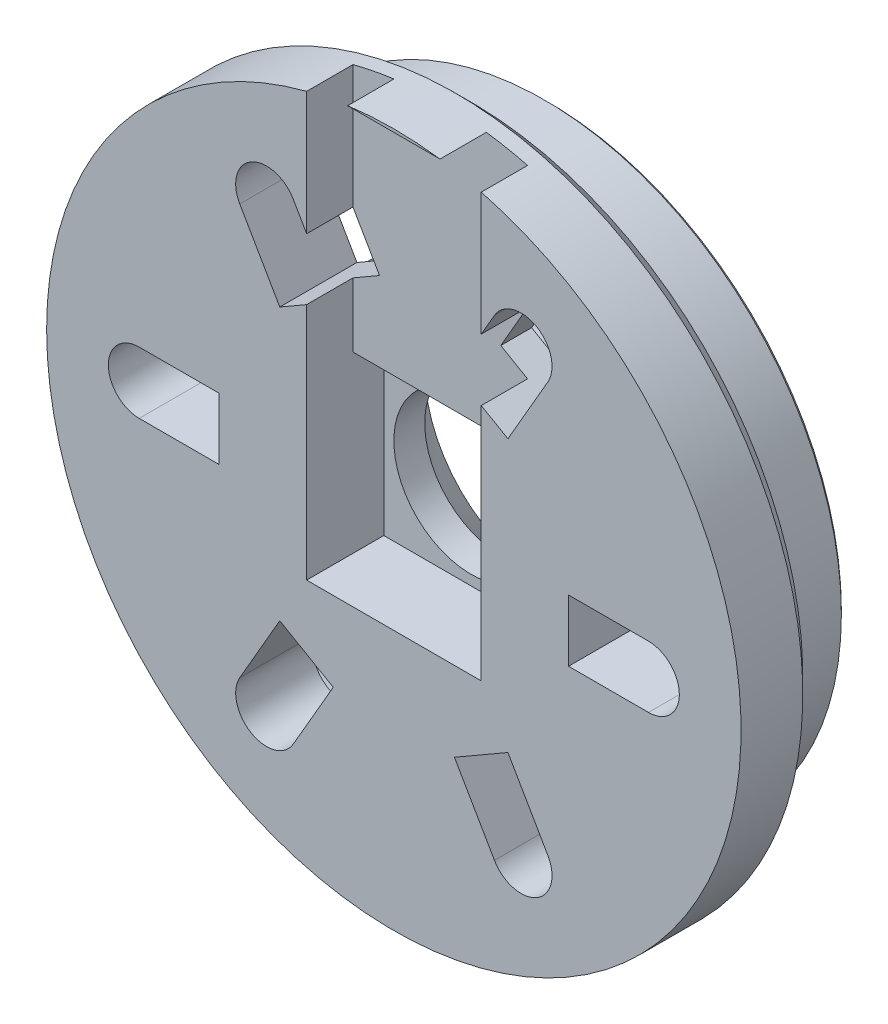
SolidWorks part; units mm, degrees
ref_plane "Front Plane" through (0, 0, 0) normal (0, 0, 1) x (1, 0, 0)
ref_plane "Top Plane" through (0, 0, 0) normal (0, 1, 0) x (1, 0, 0)
ref_plane "Right Plane" through (0, 0, 0) normal (1, 0, 0) x (0, 0, -1)
sketch "Sketch1" plane through (0, 0, 0) normal (0, 0, 1) x (1, 0, 0)
  circle A0 centre (0, 0) radius 9.8
  circle A1 centre (0, 0) radius 5
  dimension "D1" = 19.6
  dimension "D2" = 10
extrude "Boss-Extrude1" add sketch "Sketch1" along normal blind 10
sketch "Sketch2" plane through (0, 0, 10) normal (0, 0, 1) x (1, 0, 0)
  line L1 (-5.65, 5.65) -> (5.65, 5.65)
  line L2 (-5.65, 5.65) -> (-5.65, -5.65)
  line L3 (-5.65, -5.65) -> (5.65, -5.65)
  line L4 (5.65, 5.65) -> (5.65, -5.65)
  point P4 (5.65, 0)
  point P5 (0, 5.65)
  dimension "D1" = 11.3
  dimension "D2" = 11.3
extrude "Cut-Extrude1" cut sketch "Sketch2" against normal blind 5
sketch "Sketch3" plane through (0, 0, 10) normal (0, 0, 1) x (1, 0, 0)
  line L1 (-5.65, 5.65) -> (5.6634, 5.65)
  line L2 (-5.65, 5.65) -> (-5.65, 10.3571)
  line L3 (-5.65, 10.3571) -> (5.6634, 10.3571)
  line L4 (5.6634, 5.65) -> (5.6634, 10.3571)
extrude "Cut-Extrude2" cut sketch "Sketch3" against normal blind 3
sketch "Sketch4" plane through (0, 0, 10) normal (0, 0, 1) x (1, 0, 0)
  line L1 (-13.2922, 9.0382) -> (-7.8874, 9.0382)
  line L2 (-13.2922, 9.0382) -> (-13.2922, -9.0382)
  line L3 (-13.2922, -9.0382) -> (-7.8874, -9.0382)
  line L4 (-7.8874, 9.0382) -> (-7.8874, -9.0382)
  line L5 (13.4474, 9.0382) -> (7.784, 9.0382)
  line L6 (13.4474, 9.0382) -> (13.4474, -8.9089)
  line L7 (13.4474, -8.9089) -> (7.784, -8.9089)
  line L8 (7.784, 9.0382) -> (7.784, -8.9089)
extrude "Cut-Extrude3" cut sketch "Sketch4" against normal blind 3
chamfer "Chamfer1" distance 3 angle 45 1 edges at (5, 0, 0)
ref_plane "Plane1" through (0, 0, 5) normal (0, 0, -1) x (-1, 0, 0)
sketch "Sketch5" plane through (0, 0, 5) normal (0, 0, -1) x (-1, 0, 0)
  circle A0 centre (0, 0) radius 9.8
  circle A1 centre (0, 0) radius 22.5
  dimension "D1" = 12.7
extrude "Boss-Extrude2" add sketch "Sketch5" against normal blind 1
sketch "Sketch6" plane through (0, 0, 5) normal (0, 0, -1) x (-1, 0, 0)
  circle A0 centre (0, 0) radius 9.8
  circle A1 centre (0, 0) radius 11.25
  dimension "D1" = 22.5
extrude "Boss-Extrude3" add sketch "Sketch6" along normal up to surface (5 mm away) up to face at (8, 0, 0)
sketch "Sketch7" plane through (0, 0, 5) normal (0, 0, -1) x (-1, 0, 0)
  circle A0 centre (0, 0) radius 18.75
  circle A1 centre (0, 0) radius 19.25
  dimension "D1" = 37.5
  dimension "D2" = 38.5
extrude "Boss-Extrude4" add sketch "Sketch7" along normal up to surface (5 mm away) up to face at (8, 0, 0)
chamfer "Chamfer2" distance 0.25 angle 45 1 edges at (19.25, 0, 0)
sketch "Sketch9" plane through (0, 0, 6) normal (0, 0, 1) x (1, 0, 0)
  circle A0 centre (0, 0) radius 22.5
  circle A1 centre (0, 0) radius 9.8
  circle A2 centre (0, 0) radius 9.8 construction
  circle A3 centre (0, 0) radius 22.5 construction
extrude "Boss-Extrude5" add sketch "Sketch9" along normal up to surface (4 mm away) up to face at (1.1075, 1.2261, 10)
sketch "Sketch10" plane through (0, 0, 10) normal (0, 0, 1) x (1, 0, 0)
  line L1 (-5.65, 5.65) -> (5.6634, 5.65)
  line L2 (-5.65, 5.65) -> (-5.65, 22.3)
  line L3 (-5.65, 22.3) -> (5.6634, 22.3)
  line L4 (5.6634, 5.65) -> (5.6634, 22.3)
extrude "Cut-Extrude5" cut sketch "Sketch10" against normal up to surface (3 mm away) up to face at (1.1357, 6.9505, 7)
sketch "Sketch8" plane through (0, 0, 5) normal (0, 0, -1) x (-1, 0, 0)
  line L3 (-9.982, 13.2894) -> (-7.3921, 8.8035)
  line L4 (-7.3921, 8.8035) -> (-3.928, 10.8035)
  line L5 (-3.928, 10.8035) -> (-6.5179, 15.2894)
  arc A1 (-9.982, 13.2894) -> (-6.5179, 15.2894) centre (-8.25, 14.2894) cw
extrude "Cut-Extrude4" cut sketch "Sketch8" against normal through all
ref_axis "Axis1" through (0, 0, 10.5849) along (0, 0, -1)
pattern_circular "CirPattern1" count 6 over 360 about axis through (0, 0, 10.5849) along (0, 0, -1) of "Cut-Extrude4"
sketch "Sketch12" plane through (0, 0, 7) normal (0, 0, 1) x (1, 0, 0)
  line L1 (-9.9396, 6.8335) -> (-7.0029, 6.8335)
  line L2 (-9.9396, 6.8335) -> (-9.9396, -6.3817)
  line L3 (-9.9396, -6.3817) -> (-7.0029, -6.3817)
  line L4 (-7.0029, 6.8335) -> (-7.0029, -6.3817)
  line L5 (6.8899, 6.9464) -> (10.222, 6.9464)
  line L6 (6.8899, 6.9464) -> (6.8899, -6.3817)
  line L7 (6.8899, -6.3817) -> (10.222, -6.3817)
  line L8 (10.222, 6.9464) -> (10.222, -6.3817)
extrude "Boss-Extrude6" add sketch "Sketch12" along normal up to surface (3 mm away) up to face at (14.41, 0, 10)
chamfer "Chamfer3" distance 1 angle 45 1 edges at (-22.5, 0, 5)
